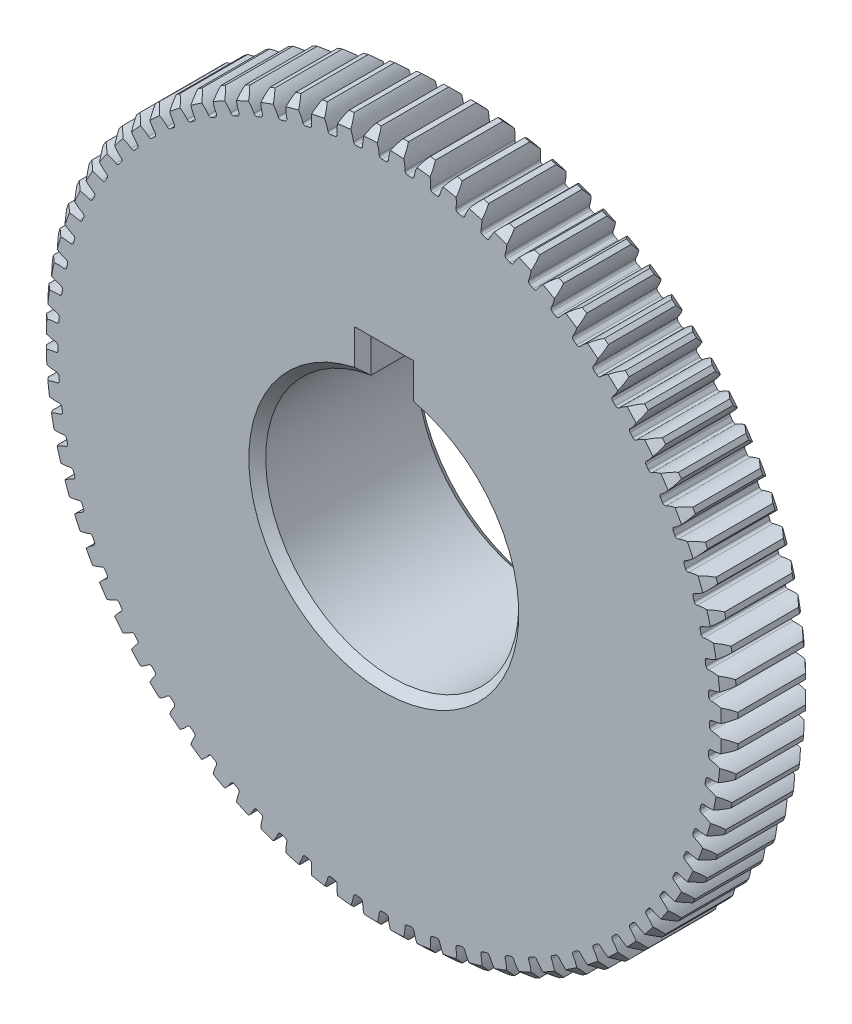
SolidWorks part; units mm, degrees
material "Plain Carbon Steel"
ref_plane "Front Plane" through (0, 0, 0) normal (0, 0, 1) x (1, 0, 0)
ref_plane "Top Plane" through (0, 0, 0) normal (0, 1, 0) x (1, 0, 0)
ref_plane "Right Plane" through (0, 0, 0) normal (1, 0, 0) x (0, 0, -1)
sketch "Sketch2" plane through (0, 0, 0) normal (0, 0, 1) x (1, 0, 0)
  circle A0 centre (0, 0) radius 40
  circle A1 centre (0, 0) radius 41
  circle A2 centre (0, 0) radius 38.6
  dimension "D1" = 80
  dimension "D2" = 82
  dimension "D3" = 2.4
extrude "Boss-Extrude1" add sketch "Sketch2" along normal mid plane 10 contours A1
sketch "Sketch3" plane through (0, 0, 0) normal (0, 0, 1) x (1, 0, 0)
  line L0 (0, 0) -> (0, 41) construction
  line L1 (-0.7853, 39.9923) -> (0.7853, 39.9923) construction
  line L2 (-0.5293, 38.5964) -> (0, 0) construction
  line L3 (0, 37.8346) -> (-1.5063, 41.973) construction
  line L4 (0, 0) -> (1.6097, 40.9684) construction
  line L5 (0.7853, 39.9923) -> (2.3548, 39.9306) construction
  circle A0 centre (0, 0) radius 41 construction
  arc A1 (-2.2312, 41.9407) -> (-0.5293, 38.5964) centre (-4.7808, 38.5381) cw
  arc A2 (2.2312, 41.9407) -> (0.5293, 38.5964) centre (4.7808, 38.5381) ccw
  circle A3 centre (0, 0) radius 38.6 construction
  arc A4 (0.5293, 38.5964) -> (-0.5293, 38.5964) centre (0, 0) ccw
  circle A6 centre (0, 0) radius 40 construction
  circle A7 centre (0, 0) radius 42
  arc A8 (2.2312, 41.9407) -> (-2.2312, 41.9407) centre (0, 0) ccw
  circle A9 centre (0, 0) radius 41 construction
  dimension "D2" = 20
  dimension "D3" = 2.25
  dimension "D1" = 1
extrude "Cut-Extrude1" cut sketch "Sketch3" against normal through all both and the other way through all
fillet "Fillet1" radius 0.3 2 edges at (0.5293, 38.5964, 0) (-0.5293, 38.5964, 0)
chamfer "Chamfer1" distance 1 2 edges at (0, -41, -5) (0, -41, 5)
pattern_circular "CirPattern1" count 80 over 360 about axis through (0, 0, 0) along (0, 0, 1) of "Fillet1", "Cut-Extrude1"
sketch "Sketch4" plane through (0, 0, 5) normal (0, 0, 1) x (1, 0, 0)
  line L0 (0, 0) -> (0, 22.6546) construction
  line L1 (2.5, 18.7902) -> (-2.5, 18.7902)
  line L2 (-2.5, 18.7902) -> (-2.5, 14.7902)
  line L3 (2.5, 18.7902) -> (2.5, 14.7902)
  arc A0 (-2.5, 14.7902) -> (2.5, 14.7902) centre (0, 0) ccw
  point P8 (0, 18.7902)
  dimension "D1" = 30
  dimension "D2" = 5
  dimension "D3" = 4
extrude "Cut-Extrude2" cut sketch "Sketch4" against normal through all
sketch "Sketch5" plane through (0, 0, -5) normal (0, 0, -1) x (-1, 0, 0)
  line L0 (-2.5, 14.7902) -> (-2.5, 18.7902) construction
  line L1 (2.5, 18.7902) -> (2.5, 14.7902) construction
  line L2 (-2.5, 18.7902) -> (2.5, 18.7902) construction
  line L3 (2.5, 18.7902) -> (2.5, 14.7902)
  line L4 (-2.5, 18.7902) -> (2.5, 18.7902)
  line L5 (-2.5, 14.7902) -> (-2.5, 18.7902)
  arc A0 (-2.5, 14.7902) -> (2.5, 14.7902) centre (0, 0) ccw construction
  arc A2 (-2.5, 14.7902) -> (2.5, 14.7902) centre (0, 0) ccw
  circle A3 centre (0, 0) radius 22.5
  dimension "D1" = 45
extrude "Boss-Extrude2" add sketch "Sketch5" along normal blind 10
chamfer "Chamfer2" distance 1 angle 45 2 edges at (22.5, 0, -5) (-22.5, 0, -15)
chamfer "Chamfer3" distance 1 angle 45 4 edges at (0, 18.7902, 5) (-2.5, 16.7902, 5) (2.5, 16.7902, 5) (0, -15, 5)
chamfer "Chamfer4" distance 1 angle 45 4 edges at (-2.5, 16.7902, -15) (0, 18.7902, -15) (2.5, 16.7902, -15) (0, -15, -15)
equation "\"Module\"= 1mm"
equation "\"Number of Teeth\"= 80"
equation "\"D1@Sketch2\"=\"Module\" * \"Number of Teeth\""
equation "\"D2@Sketch2\"=(\"Number of Teeth\" + 2) * \"Module\""
equation "\"D3@Sketch2\"=\"Module\" * if( \"Module\" => 1.25, 2.25, 2.4) "
equation "\"D3@Sketch3\"=180deg / \"Number of Teeth\""
equation "\"D1@Fillet1\"=0.3 * \"Module\""
equation "\"D1@CirPattern1\"=\"Number of Teeth\""
equation "\"D1@Chamfer1\"=\"Module\""
equation "\"Pressure Angle\"= 20deg"
equation "\"D2@Sketch3\"=\"Pressure Angle\""
